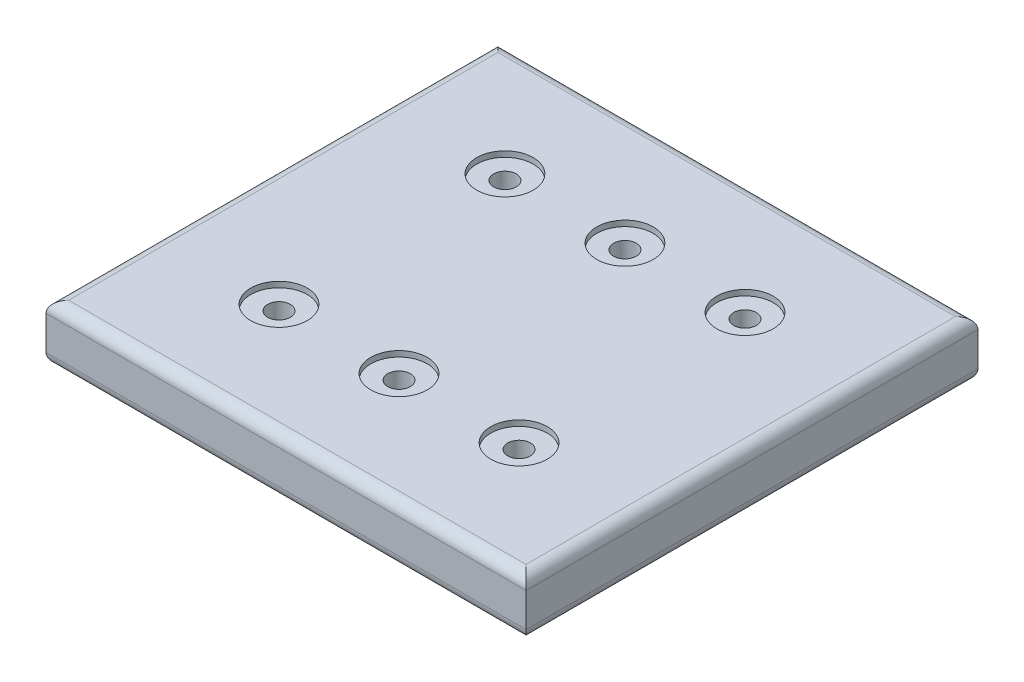
SolidWorks part; units mm, degrees
note: The reader was unsure of these and kept them because the rebuilt part matched: shared geometry of "草图2<2>".
ref_plane "Front" through (0, 0, 0) normal (0, 0, 1) x (1, 0, 0)
ref_plane "Top" through (0, 0, 0) normal (0, 1, 0) x (1, 0, 0)
ref_plane "Right" through (0, 0, 0) normal (1, 0, 0) x (0, 0, -1)
sketch "草图1" plane through (0, 0, 0) normal (0, 1, 0) x (1, 0, 0)
  line L1 (-45.2449, 62.0215) -> (39.7551, 62.0215)
  line L2 (-45.2449, 62.0215) -> (-45.2449, -17.9785)
  line L3 (-45.2449, -17.9785) -> (39.7551, -17.9785)
  line L4 (39.7551, 62.0215) -> (39.7551, -17.9785)
extrude "凸台-拉伸1" add sketch "草图1" along normal blind 10
sketch "草图2" plane through (0, 10, 0) normal (0, 1, 0) x (1, 0, 0)
  line L0 (39.7551, 62.0215) -> (39.7551, 42.0215) construction
  line L1 (39.7551, -17.9785) -> (39.7551, 62.0215) construction
  line L2 (39.7551, 42.0215) -> (-45.2449, 42.0215) construction
  line L3 (-45.2449, 62.0215) -> (-45.2449, -17.9785) construction
  line L4 (39.7551, -17.9785) -> (39.7551, 2.0215) construction
  line L5 (39.7551, 2.0215) -> (-45.2449, 2.0215) construction
  line L6 (-45.2449, 42.0215) -> (-2.7449, 42.0215) construction
  line L7 (-45.2449, 2.0215) -> (-2.7449, 2.0215) construction
  line L8 (-2.7449, 42.0215) -> (39.7551, 42.0215) construction
  line L9 (-2.7449, 2.0215) -> (39.7551, 2.0215) construction
  line L10 (-45.2449, 2.0215) -> (-23.9949, 20.0467) construction
  line L11 (-23.9949, 20.0467) -> (-2.7449, 2.0215) construction
  line L12 (-2.7449, 2.0215) -> (-23.9949, 20.0467) construction
  line L13 (-23.9949, 20.0467) -> (-23.9949, 2.0215) construction
  line L14 (-23.9949, 2.0215) -> (-23.9949, 42.0215) construction
  line L15 (-23.9949, 42.0215) -> (19.8196, 42.0215) construction
  line L16 (-2.7449, 2.0215) -> (18.5051, 19.672) construction
  line L17 (9.3642, 2.0215) -> (27.4613, 2.0215) construction
  line L18 (18.5051, 19.672) -> (39.7551, 2.0215) construction
  line L19 (39.7551, 2.0215) -> (18.5051, 19.672) construction
  line L20 (18.5051, 19.672) -> (18.5051, 2.0215) construction
  line L21 (18.5051, 2.0215) -> (18.5051, 42.0215) construction
  circle A0 centre (-2.7449, 42.0215) radius 5
  circle A1 centre (-2.7449, 2.0215) radius 5
  circle A2 centre (-23.9949, 2.0215) radius 5
  circle A3 centre (18.5051, 2.0215) radius 5
  circle A4 centre (18.5051, 42.0215) radius 5
  circle A5 centre (-23.9949, 42.0215) radius 5
  circle A6 centre (18.5051, 42.0215) radius 2
  circle A7 centre (-2.7449, 42.0215) radius 2
  circle A8 centre (-23.9949, 42.0215) radius 2
  circle A9 centre (-23.9949, 2.0215) radius 2
  circle A10 centre (-2.7449, 2.0215) radius 2
  circle A11 centre (18.5051, 2.0215) radius 2
ref_point "点5"
ref_point "点6"
ref_point "点7"
ref_point "点8"
ref_point "点9"
ref_point "点10"
ref_point "点11"
ref_point "点12"
extrude "切除-拉伸1" cut sketch "草图2" against normal blind 1
extrude "切除-拉伸2" cut sketch "草图2<2>" against normal through all contours A8 | A7 | A6 | A9 | A10 | A11
sketch "草图2<2>" plane through (0, 10, 0) normal (0, 1, 0) x (1, 0, 0) same geometry as "草图2"
sketch "草图3" plane through (0, 0, 0) normal (0, -1, 0) x (-1, 0, 0)
  line L0 (-39.7551, 62.0215) -> (45.2449, -17.9785) construction
  line L1 (45.2449, -17.9785) -> (-39.7551, -17.9785) construction
  line L2 (-39.7551, -17.9785) -> (45.2449, 62.0215) construction
  circle A0 centre (2.7449, 22.0215) radius 15
extrude "切除-拉伸3" cut sketch "草图3" against normal blind 5
fillet "圆角1" radius 0.5 1 edges at (-2.7449, 0, -37.0215)
fillet "圆角2" radius 2 4 edges at (-2.7449, 0, -62.0215) (39.7551, 0, -22.0215) (-2.7449, 0, 17.9785) (-45.2449, 0, -22.0215)
fillet "圆角3" radius 2 4 edges at (39.7551, 10, -22.0215) (-2.7449, 10, -62.0215) (-45.2449, 10, -22.0215) (-2.7449, 10, 17.9785)
